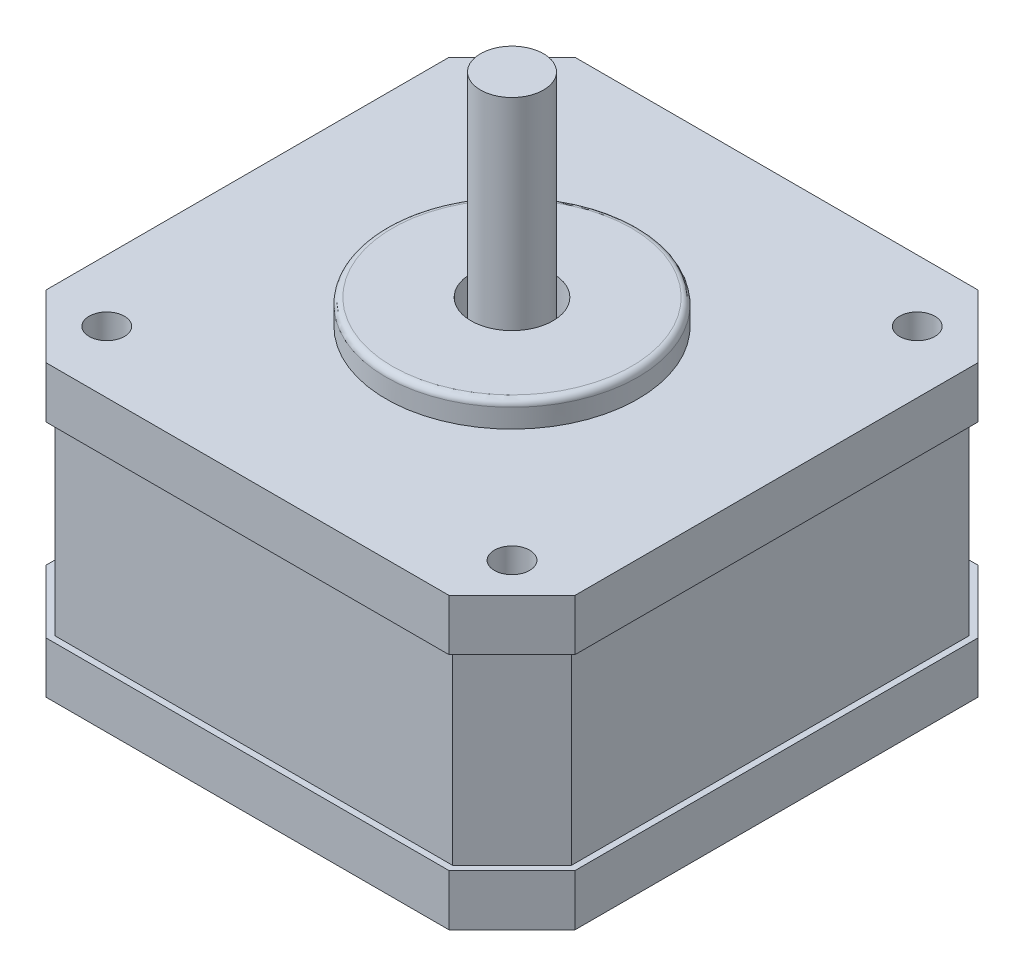
SolidWorks part; units mm, degrees
ref_plane "Ön Düzlem" through (0, 0, 0) normal (0, 0, 1) x (1, 0, 0)
ref_plane "Üst Düzlem" through (0, 0, 0) normal (0, 1, 0) x (1, 0, 0)
ref_plane "Sağ Düzlem" through (0, 0, 0) normal (1, 0, 0) x (0, 0, -1)
sketch "Çizim1" plane through (0, 0, 0) normal (0, 1, 0) x (1, 0, 0)
  line L1 (-21, -21) -> (21, -21)
  line L2 (-21, -21) -> (-21, 21)
  line L3 (-21, 21) -> (21, 21)
  line L4 (21, -21) -> (21, 21)
  line L5 (-21, -21) -> (21, 21) construction
  line L6 (-21, 21) -> (21, -21) construction
  point P0 (0, 0)
  dimension "D1" = 42
  dimension "D2" = 42
extrude "Yükseklik-Ekstrüzyon1" add sketch "Çizim1" along normal blind 23
sketch "Çizim2" plane through (0, 0, 21) normal (0, 0, 1) x (1, 0, 0)
  line L0 (23.1, 0) -> (-23.1, 0) construction
  line L1 (-36.7941, 4.0777) -> (34.8147, 4.0777)
  line L2 (-36.7941, 4.0777) -> (-36.7941, 18.9223)
  line L3 (-36.7941, 18.9223) -> (34.8147, 18.9223)
  line L4 (34.8147, 4.0777) -> (34.8147, 18.9223)
  line L5 (-36.7941, 4.0777) -> (34.8147, 18.9223) construction
  line L6 (-36.7941, 18.9223) -> (34.8147, 4.0777) construction
  point P0 (-0.9897, 11.5)
extrude "Kes-Ekstrüzyon1" cut sketch "Çizim2" against normal blind 0.5
chamfer "Pah1" distance 5 angle 45 2 edges at (-21, 2.0389, 21) (-21, 20.9611, 21)
chamfer "Pah2" distance 5 angle 45 2 edges at (21, 2.0389, 21) (21, 20.9611, 21)
chamfer "Pah3" distance 5 angle 45 1 edges at (21, 11.5, -21)
chamfer "Pah4" distance 5 angle 45 1 edges at (-21, 11.5, -21)
ref_plane "Düzlem1" through (-25.5711, 0, 25.5711) normal (-0.7071, 0, 0.7071) x (0.7071, 0, 0.7071)
sketch "Çizim3" plane through (-25.5711, 0, 25.5711) normal (-0.7071, 0, 0.7071) x (0.7071, 0, 0.7071)
  line L0 (3.5355, 18.9223) -> (26.163, 18.9223) construction
  line L1 (-5.7024, 4.0777) -> (5.7024, 4.0777)
  line L2 (-5.7024, 4.0777) -> (-5.7024, 18.9223)
  line L3 (-5.7024, 18.9223) -> (5.7024, 18.9223)
  line L4 (5.7024, 4.0777) -> (5.7024, 18.9223)
  line L5 (-5.7024, 4.0777) -> (5.7024, 18.9223) construction
  line L6 (-5.7024, 18.9223) -> (5.7024, 4.0777) construction
  point P0 (0, 11.5)
extrude "Kes-Ekstrüzyon2" cut sketch "Çizim3" against normal blind 10.5 contours L2 L3 L4 L1
mirror "Aynalama1" about plane through (0, 0, 0) normal (0, 0, 1) of "Kes-Ekstrüzyon2", "Kes-Ekstrüzyon1"
mirror "Aynalama2" about plane through (0, 0, 0) normal (1, 0, 0) of "Kes-Ekstrüzyon2"
sketch "Çizim6" plane through (21, 0, 0) normal (1, 0, 0) x (0, 0, -1)
  line L1 (-24.2519, 4.0777) -> (24.2519, 4.0777)
  line L2 (-24.2519, 4.0777) -> (-24.2519, 18.9223)
  line L3 (-24.2519, 18.9223) -> (24.2519, 18.9223)
  line L4 (24.2519, 4.0777) -> (24.2519, 18.9223)
  line L5 (-24.2519, 4.0777) -> (24.2519, 18.9223) construction
  line L6 (-24.2519, 18.9223) -> (24.2519, 4.0777) construction
  point P0 (0, 11.5)
extrude "Kes-Ekstrüzyon3" cut sketch "Çizim6" against normal blind 0.5
sketch "Çizim7" plane through (-21, 0, 0) normal (-1, 0, 0) x (0, 0, 1)
  line L0 (21, 18.9223) -> (16, 18.9223) construction
  line L1 (-19.0914, 4.0777) -> (19.0914, 4.0777)
  line L2 (-19.0914, 4.0777) -> (-19.0914, 18.9223)
  line L3 (-19.0914, 18.9223) -> (19.0914, 18.9223)
  line L4 (19.0914, 4.0777) -> (19.0914, 18.9223)
  line L5 (-19.0914, 4.0777) -> (19.0914, 18.9223) construction
  line L6 (-19.0914, 18.9223) -> (19.0914, 4.0777) construction
  point P0 (0, 11.5)
extrude "Kes-Ekstrüzyon4" cut sketch "Çizim7" against normal blind 0.5
mirror "Aynalama3" about plane through (0, 0, 0) normal (0, 0, 1) of "Aynalama2"
ref_plane "Düzlem3" through (0, 23, 0) normal (0, 1, 0) x (1, 0, 0)
sketch "Çizim8" plane through (0, 23, 0) normal (0, 1, 0) x (1, 0, 0)
  line L0 (0, 24.6528) -> (0, -27.5404) construction
  line L1 (29.7866, 0) -> (-34.5512, 0) construction
  circle A0 centre (-16.0876, 16.0876) radius 1.3994
  circle A1 centre (16.0876, 16.0876) radius 1.3994
  circle A2 centre (16.0876, -16.0876) radius 1.3994
  circle A3 centre (-16.0876, -16.0876) radius 1.3994
extrude "Kes-Ekstrüzyon5" cut sketch "Çizim8" against normal blind 5
sketch "Çizim9" plane through (0, 23, 0) normal (0, 1, 0) x (1, 0, 0)
  circle A0 centre (0, 0) radius 10
  dimension "D1" = 20
extrude "Yükseklik-Ekstrüzyon2" add sketch "Çizim9" along normal blind 2
sketch "Çizim10" plane through (0, 23, 0) normal (0, 1, 0) x (1, 0, 0)
  circle A0 centre (0, 0) radius 3.25
  dimension "D1" = 6.5
extrude "Kes-Ekstrüzyon6" cut sketch "Çizim10" against normal blind 2.5 and the other way blind 5
sketch "Çizim11" plane through (0, 20.5, 0) normal (0, 1, 0) x (1, 0, 0)
  circle A0 centre (0, 0) radius 2.5
  dimension "D1" = 5
extrude "Yükseklik-Ekstrüzyon3" add sketch "Çizim11" along normal blind 20
fillet "Radyus2" radius 0.5 1 edges at (0, 25, 10)
